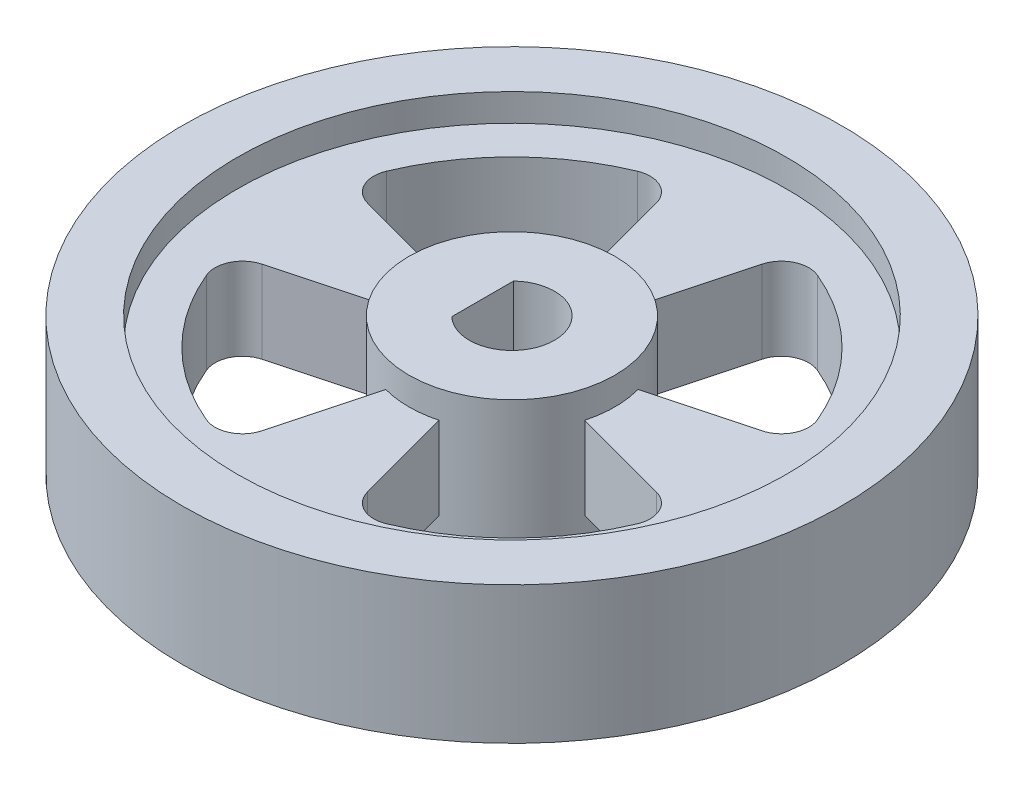
SolidWorks part; units mm, degrees
ref_plane "前视基准面" through (0, 0, 0) normal (0, 0, 1) x (1, 0, 0)
ref_plane "上视基准面" through (0, 0, 0) normal (0, 1, 0) x (1, 0, 0)
ref_plane "右视基准面" through (0, 0, 0) normal (1, 0, 0) x (0, 0, -1)
other "Configuration Table"
sketch "草图1" plane through (0, 0, 0) normal (0, 1, 0) x (1, 0, 0)
  line L0 (-2.1325, 2.25) -> (-2.1325, -2.25)
  arc A0 (-2.1325, -2.25) -> (-2.1325, 2.25) centre (0, 0) ccw
  circle A1 centre (0, 0) radius 20
  circle A2 centre (0, 0) radius 24
  circle A3 centre (0, 0) radius 7.5
  dimension "D1" = 6.2
  dimension "D3" = 15
  dimension "D4" = 48
  dimension "D5" = 40
  dimension "D2" = 4.5
extrude "凸台-拉伸1" add sketch "草图1" along normal blind 5 and the other way blind 5 contours A3 A0 L0 | A2 A1 region at (-23.3212, 0, 0) region at (-7.2879, 0, 0)
extrude "凸台-拉伸2" add sketch "草图1<4>" along normal blind 3 and the other way blind 3 contours A1 A3 region at (-19.4343, 0, 0)
sketch "草图1<4>" plane through (0, 0, 0) normal (0, 1, 0) x (1, 0, 0) same geometry as "草图1"
sketch "草图3" plane through (0, 3, 0) normal (0, 1, 0) x (1, 0, 0)
  line L0 (0, -32.003) -> (0, 32.003) construction
  line L1 (-31.5123, 0) -> (31.5123, 0) construction
  line L2 (0, 0) -> (3.8476, 14.3595)
  line L3 (0, 0) -> (14.3595, 3.8476)
  line L4 (0, 0) -> (3.8476, -14.3595)
  line L5 (0, 0) -> (14.3595, -3.8476)
  line L6 (0, 0) -> (-14.3595, -3.8476)
  line L7 (0, 0) -> (-3.8476, -14.3595)
  line L8 (0, 0) -> (-3.8476, 14.3595)
  line L9 (0, 0) -> (-14.3595, 3.8476)
  arc A0 (1.9411, 7.2444) -> (7.2444, 1.9411) centre (0, 0) cw
  arc A1 (6.5501, 15.6875) -> (15.6875, 6.5501) centre (0, 0) cw
  arc A2 (6.5501, 15.6875) -> (3.8476, 14.3595) centre (5.7795, 13.8419) ccw
  arc A3 (14.3595, 3.8476) -> (15.6875, 6.5501) centre (13.8419, 5.7795) ccw
  arc A4 (3.8476, -14.3595) -> (6.5501, -15.6875) centre (5.7795, -13.8419) ccw
  arc A5 (15.6875, -6.5501) -> (6.5501, -15.6875) centre (0, 0) cw
  arc A6 (15.6875, -6.5501) -> (14.3595, -3.8476) centre (13.8419, -5.7795) ccw
  arc A7 (-14.3595, -3.8476) -> (-15.6875, -6.5501) centre (-13.8419, -5.7795) ccw
  arc A8 (-6.5501, -15.6875) -> (-15.6875, -6.5501) centre (0, 0) cw
  arc A9 (-6.5501, -15.6875) -> (-3.8476, -14.3595) centre (-5.7795, -13.8419) ccw
  arc A10 (-3.8476, 14.3595) -> (-6.5501, 15.6875) centre (-5.7795, 13.8419) ccw
  arc A11 (-15.6875, 6.5501) -> (-6.5501, 15.6875) centre (0, 0) cw
  arc A12 (-15.6875, 6.5501) -> (-14.3595, 3.8476) centre (-13.8419, 5.7795) ccw
  point P4 (0, 0)
  point P8 (0, 0)
  point P37 (0, 0)
  circle M2 centre (0, 0) radius 7.5
  dimension "D3" = 7.5
  dimension "D4" = 17
  dimension "D5" = 2
  dimension "D6" = 2
  dimension "D1" = 15
  dimension "D2" = 15
  dimension "D7" = 4
extrude "切除-拉伸2" cut sketch "草图3" against normal blind 6 contours A11 A12 L9 L8 A10 M2 | A8 A9 L7 L6 A7 M2 | L3 A3 A1 A2 L2 M2 | A5 A6 L5 L4 A4 M2 region at (8.6581, 3, -8.6581) region at (8.6581, 3, 8.6581) region at (-8.6581, 3, 8.6581) region at (-8.6581, 3, -8.6581)
